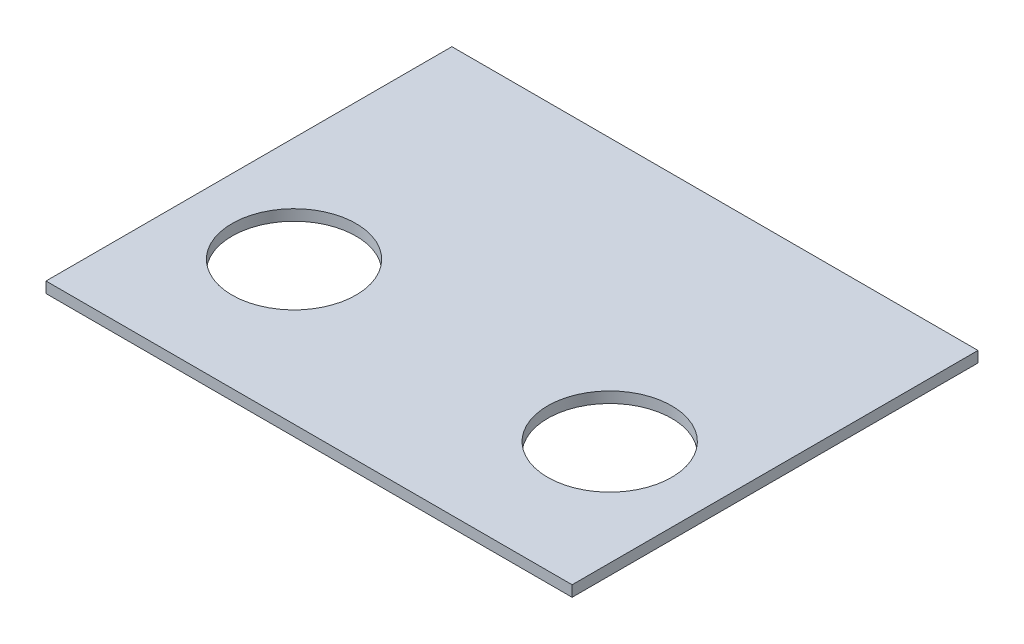
SolidWorks part; units mm, degrees
ref_plane "Plan de face" through (0, 0, 0) normal (0, 0, 1) x (1, 0, 0)
ref_plane "Plan de dessus" through (0, 0, 0) normal (0, 1, 0) x (1, 0, 0)
ref_plane "Plan de droite" through (0, 0, 0) normal (1, 0, 0) x (0, 0, -1)
sketch "Esquisse1" plane through (0, 0, 0) normal (0, 1, 0) x (1, 0, 0)
  line L1 (-35, 27) -> (35, 27)
  line L2 (-35, 27) -> (-35, -27)
  line L3 (-35, -27) -> (35, -27)
  line L4 (35, 27) -> (35, -27)
  line L5 (-35, 27) -> (35, -27) construction
  line L6 (-35, -27) -> (35, 27) construction
  point P0 (0, 0)
  dimension "D1" = 54
  dimension "D2" = 70
extrude "Boss.-Extru.1" add sketch "Esquisse1" along normal blind 1.45
sketch "Esquisse2" plane through (0, 1.45, 0) normal (0, 1, 0) x (1, 0, 0)
  line L0 (-35, -27) -> (35, -27) construction
  line L1 (-35, 27) -> (-35, -27) construction
  circle A0 centre (-21, -8) radius 8.25
  point P6 (0, 0)
  point P7 (0, 0)
  dimension "D1" = 16.5
  dimension "D2" = 19
  dimension "D3" = 14
extrude "Enlèv. mat.-Extru.1" cut sketch "Esquisse2" against normal blind 10
sketch "Esquisse4" plane through (0, 1.45, 0) normal (0, 1, 0) x (1, 0, 0)
  line L0 (35, -27) -> (35, 27) construction
  line L1 (-35, -27) -> (35, -27) construction
  circle A0 centre (21, -8) radius 8.25
  dimension "D1" = 16.5
  dimension "D2" = 14
  dimension "D3" = 19
extrude "Enlèv. mat.-Extru.3" cut sketch "Esquisse4" against normal blind 10
